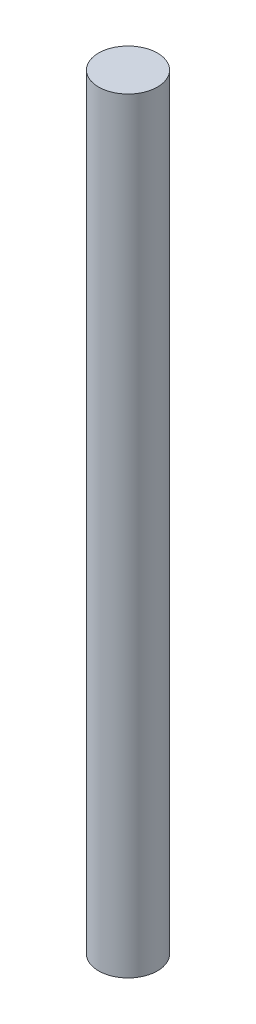
SolidWorks part; units mm, degrees
ref_plane "Front Plane" through (0, 0, 0) normal (0, 0, 1) x (1, 0, 0)
ref_plane "Top Plane" through (0, 0, 0) normal (0, 1, 0) x (1, 0, 0)
ref_plane "Right Plane" through (0, 0, 0) normal (1, 0, 0) x (0, 0, -1)
ref_axis "X" through (-88.99, 0, 0) along (1, 0, 0)
ref_axis "Y" through (0, 55, 0) along (0, -1, 0)
ref_axis "Z" through (0, 0, -88.99) along (0, 0, 1)
sketch "Sketch1" plane through (0, 0, 0) normal (0, 1, 0) x (1, 0, 0)
  circle A0 centre (0, 0) radius 1
  dimension "D1" = 2
extrude "Boss-Extrude1" add sketch "Sketch1" along normal blind 26
